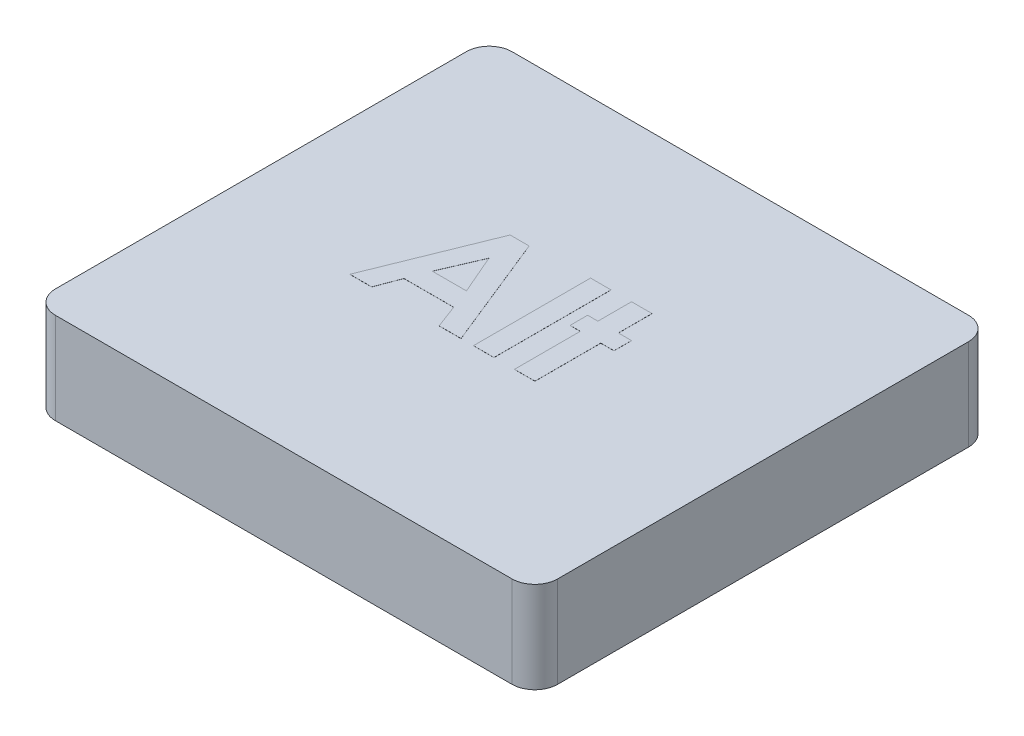
SolidWorks part; units mm, degrees
ref_plane "Front Plane" through (0, 0, 0) normal (0, 0, 1) x (1, 0, 0)
ref_plane "Top Plane" through (0, 0, 0) normal (0, 1, 0) x (1, 0, 0)
ref_plane "Right Plane" through (0, 0, 0) normal (1, 0, 0) x (0, 0, -1)
sketch "Sketch1" plane through (0, 0, 0) normal (0, 1, 0) x (1, 0, 0)
  line L0 (0, 0) -> (13.97, 0)
  line L1 (13.97, 0) -> (13.97, 12.7)
  line L2 (13.97, 12.7) -> (0, 12.7)
  line L3 (0, 12.7) -> (0, 0)
  dimension "D1" = 13.97
  dimension "D2" = 12.7
extrude "Boss-Extrude1" add sketch "Sketch1" along normal blind 2.54
fillet "Fillet1" radius 0.635 4 edges at (0, 1.27, -12.7) (13.97, 1.27, -12.7) (13.97, 1.27, 0) (0, 1.27, 0)
shell "Shell1" thickness 0.635 removed face at (6.985, 0, -6.35)
sketch "Sketch2" plane through (0, 1.905, 0) normal (0, -1, 0) x (-1, 0, 0)
  line L0 (-0.635, 6.35) -> (-13.335, 6.35) construction
  line L1 (-0.635, 12.065) -> (-0.635, 0.635) construction
  line L2 (-13.335, 0.635) -> (-13.335, 12.065) construction
  line L3 (-6.985, 0.635) -> (-6.985, 12.065) construction
  line L4 (-0.635, 0.635) -> (-13.335, 0.635) construction
  line L5 (-13.335, 12.065) -> (-0.635, 12.065) construction
  circle A0 centre (-6.985, 6.35) radius 2.54
  dimension "D1" = 5.08
extrude "Boss-Extrude2" add sketch "Sketch2" along normal up to surface (1.905 mm away) up to face at (6.985, 0, -6.35)
sketch "Sketch3" plane through (0, 2.54, 0) normal (0, 1, 0) x (1, 0, 0)
  line L0 (0, 12.065) -> (0, 0.635) construction
  line L1 (13.335, 12.7) -> (0.635, 12.7) construction
  text T0 "<b>Alt</b>"
  dimension "D1" = 3.683
  dimension "D2" = 7.62
extrude "Boss-Extrude3" add sketch "Sketch3" along normal blind 0.0025
